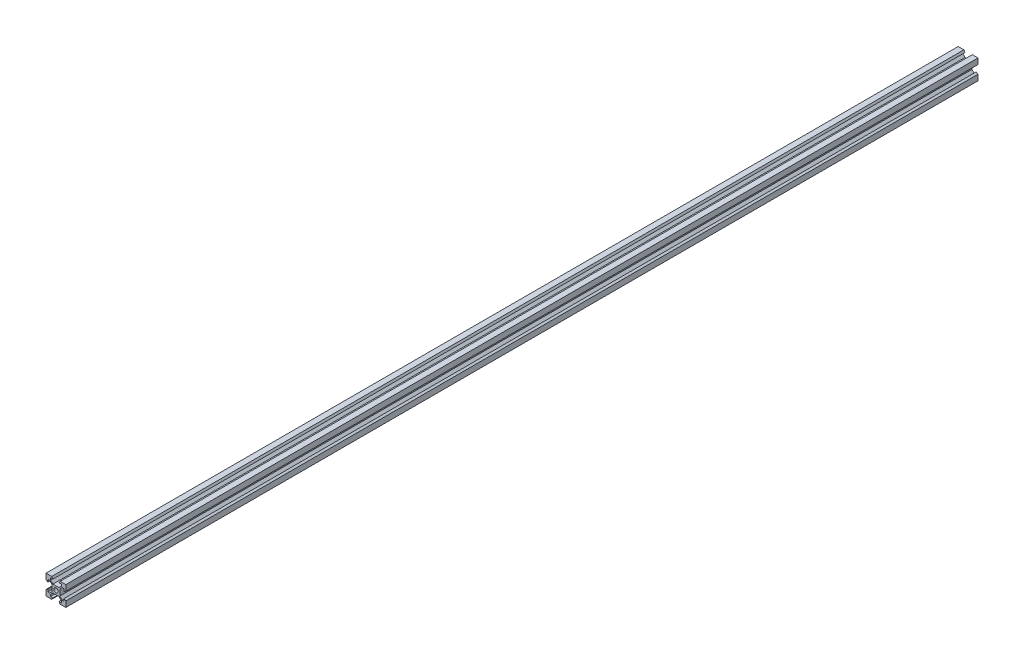
SolidWorks part; units mm, degrees
ref_plane "Front Plane" through (0, 0, 0) normal (0, 0, 1) x (1, 0, 0)
ref_plane "Top Plane" through (0, 0, 0) normal (0, 1, 0) x (1, 0, 0)
ref_plane "Right Plane" through (0, 0, 0) normal (1, 0, 0) x (0, 0, -1)
sketch "Sketch1" plane through (0, 0, 0) normal (0, 0, 1) x (1, 0, 0)
  line L0 (-10, 10) -> (-4.25, 10)
  line L1 (-4.25, 10) -> (-3.065, 8.2)
  line L2 (-3.065, 8.2) -> (-5.5, 8.2)
  line L3 (-5.5, 8.2) -> (-5.5, 6.3485)
  line L4 (-5.5, 6.3485) -> (-3.0515, 3.9)
  line L5 (-3.0515, 3.9) -> (0, 3.9)
  line L6 (-10, 10) -> (0, 0) construction
  line L7 (-3.9, 3.0515) -> (-3.9, 0)
  line L8 (-6.3485, 5.5) -> (-3.9, 3.0515)
  line L9 (-8.2, 3.065) -> (-8.2, 5.5)
  line L10 (-8.2, 5.5) -> (-6.3485, 5.5)
  line L11 (-10, 4.25) -> (-8.2, 3.065)
  line L12 (-10, 10) -> (-10, 4.25)
  line L13 (10, 10) -> (10, 4.25)
  line L14 (10, 10) -> (4.25, 10)
  line L15 (4.25, 10) -> (3.065, 8.2)
  line L16 (3.065, 8.2) -> (5.5, 8.2)
  line L17 (5.5, 8.2) -> (5.5, 6.3485)
  line L18 (8.2, 5.5) -> (6.3485, 5.5)
  line L19 (8.2, 3.065) -> (8.2, 5.5)
  line L20 (10, 4.25) -> (8.2, 3.065)
  line L21 (3.9, 3.0515) -> (3.9, 0)
  line L22 (6.3485, 5.5) -> (3.9, 3.0515)
  line L23 (5.5, 6.3485) -> (3.0515, 3.9)
  line L24 (3.0515, 3.9) -> (0, 3.9)
  line L25 (10, -10) -> (4.25, -10)
  line L26 (10, -10) -> (10, -4.25)
  line L27 (10, -4.25) -> (8.2, -3.065)
  line L28 (8.2, -3.065) -> (8.2, -5.5)
  line L29 (8.2, -5.5) -> (6.3485, -5.5)
  line L30 (5.5, -8.2) -> (5.5, -6.3485)
  line L31 (3.065, -8.2) -> (5.5, -8.2)
  line L32 (4.25, -10) -> (3.065, -8.2)
  line L33 (3.0515, -3.9) -> (0, -3.9)
  line L34 (5.5, -6.3485) -> (3.0515, -3.9)
  line L35 (6.3485, -5.5) -> (3.9, -3.0515)
  line L36 (3.9, -3.0515) -> (3.9, 0)
  line L37 (-10, -10) -> (-10, -4.25)
  line L38 (-10, -10) -> (-4.25, -10)
  line L39 (-4.25, -10) -> (-3.065, -8.2)
  line L40 (-3.065, -8.2) -> (-5.5, -8.2)
  line L41 (-5.5, -8.2) -> (-5.5, -6.3485)
  line L42 (-8.2, -5.5) -> (-6.3485, -5.5)
  line L43 (-8.2, -3.065) -> (-8.2, -5.5)
  line L44 (-10, -4.25) -> (-8.2, -3.065)
  line L45 (-3.9, -3.0515) -> (-3.9, 0)
  line L46 (-6.3485, -5.5) -> (-3.9, -3.0515)
  line L47 (-5.5, -6.3485) -> (-3.0515, -3.9)
  line L48 (-3.0515, -3.9) -> (0, -3.9)
  circle A0 centre (0, 0) radius 2.1
  point P58 (0, 0)
  dimension "D1" = 4.2
  dimension "D2" = 10
  dimension "D3" = 10
  dimension "D4" = 6.1
  dimension "D5" = 4.3
  dimension "D6" = 3.065
  dimension "D7" = 5.5
  dimension "D8" = 1.2
  dimension "D9" = 4.25
  dimension "D10" = 4
extrude "Boss-Extrude1" add sketch "Sketch1" along normal blind 920
